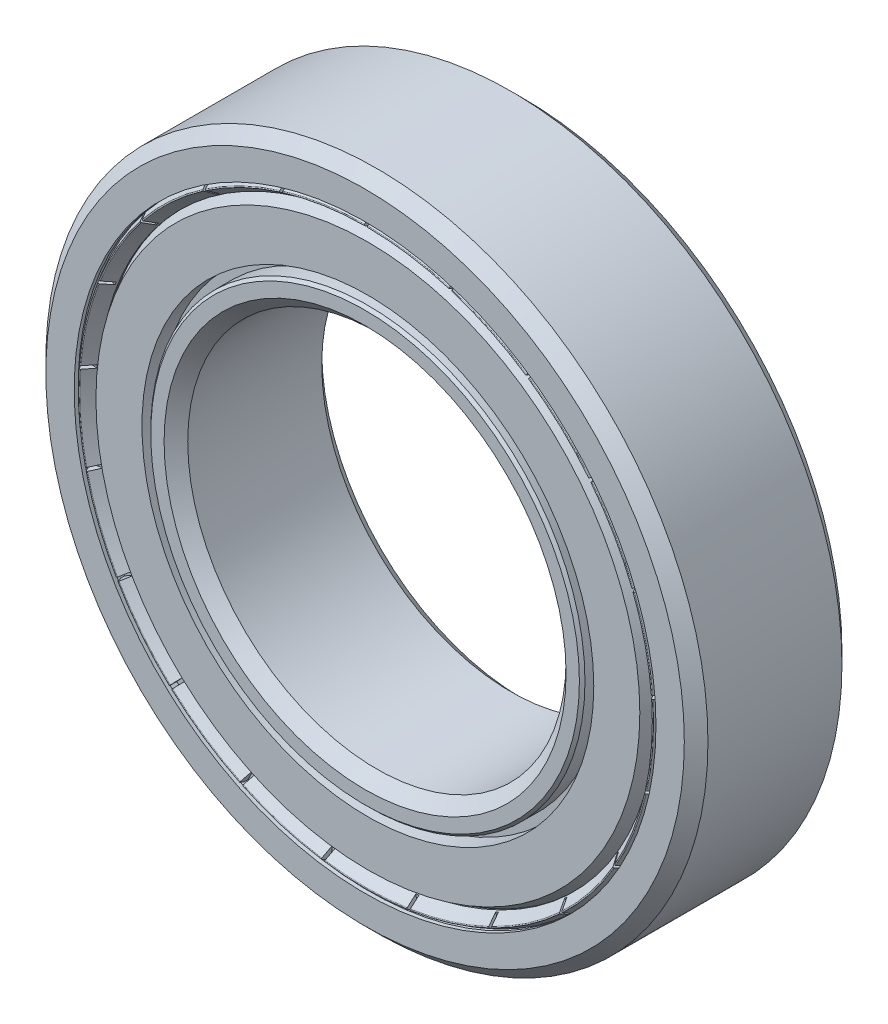
SolidWorks part; units mm, degrees
ref_plane "Front Plane" through (0, 0, 0) normal (0, 0, 1) x (1, 0, 0)
ref_plane "Top Plane" through (0, 0, 0) normal (0, 1, 0) x (1, 0, 0)
ref_plane "Right Plane" through (0, 0, 0) normal (1, 0, 0) x (0, 0, -1)
sketch "Sketch1" plane through (0, 0, 0) normal (0, 0, 1) x (1, 0, 0)
  circle A0 centre (0, 0) radius 6
  circle A1 centre (0, 0) radius 10.5
  dimension "OD" = 21
  dimension "ID" = 12
sketch "Sketch2" plane through (0, 0, 0) normal (1, 0, 0) x (0, 0, -1)
  line L0 (-2.5, 10.5) -> (2.5, 10.5)
  line L1 (-2.5, 6) -> (-2.5, -6) construction
  line L2 (2.5, 10.5) -> (2.5, -10.5) construction
  line L3 (-2.5, 0) -> (2.5, 0) construction
  line L6 (0, 10.5) -> (0, 6) construction
  circle A0 centre (0, 8.25) radius 1.575 construction
  point P8 (0, 10.5)
  dimension "Approx. Ball Dia." = 3.15
  dimension "Width" = 5
  dimension "For Shaft Diameter" = 12
  dimension "For Housing ID" = 21
sketch "Sketch3" plane through (0, 0, 0) normal (1, 0, 0) x (0, 0, -1)
  line L0 (0, 0) -> (0, 12) construction
  line L1 (-2.5, 6) -> (-2.5, -6) construction
  line L2 (2.125, 10.5) -> (-2.125, 10.5)
  line L3 (-2.125, 10.5) -> (-2.5, 10.125)
  line L4 (-2.5, 10.125) -> (-2.5, 9.2262)
  line L5 (-2.5, 9.2262) -> (-2.375, 9.2262)
  line L6 (-2.375, 9.2262) -> (-2.375, 9.5256)
  line L7 (-2.375, 9.5256) -> (-2.2866, 9.614)
  line L8 (-2.2866, 9.614) -> (-0.7875, 9.614)
  line L10 (-2.5, 10.5) -> (2.5, 10.5) construction
  line L12 (-2.375, 9.5256) -> (-2.375, 9.825) construction
  line L13 (2.2866, 9.614) -> (0.7875, 9.614)
  line L14 (2.375, 9.5256) -> (2.2866, 9.614)
  line L15 (2.375, 9.2262) -> (2.375, 9.5256)
  line L16 (2.5, 9.2262) -> (2.375, 9.2262)
  line L17 (2.5, 10.125) -> (2.5, 9.2262)
  line L18 (2.125, 10.5) -> (2.5, 10.125)
  line L19 (2.125, 6) -> (-2.125, 6)
  line L20 (-2.125, 6) -> (-2.5, 6.375)
  line L21 (-2.5, 6.375) -> (-2.5, 6.7976)
  line L22 (-2.5, 6.7976) -> (-2.4116, 6.886)
  line L23 (-2.4116, 6.886) -> (-0.7875, 6.886)
  line L25 (2.4116, 6.886) -> (0.7875, 6.886)
  line L26 (2.5, 6.7976) -> (2.4116, 6.886)
  line L27 (2.5, 6.375) -> (2.5, 6.7976)
  line L28 (2.125, 6) -> (2.5, 6.375)
  circle A2 centre (0, 8.25) radius 1.575 construction
  arc A3 (-0.7875, 9.614) -> (0.7875, 9.614) centre (0, 8.25) cw
  arc A4 (-0.7875, 6.886) -> (0.7875, 6.886) centre (0, 8.25) ccw
  point P5 (0, 9.825)
  point P31 (0, 10.5)
  point P37 (0, 6)
  dimension "D1" = 45
  dimension "D2" = 0.125
  dimension "D3" = 1.575
  dimension "D4" = 0.375
revolve "Revolve1" add sketch "Sketch3" angle 360 about L3
sketch "Sketch4" plane through (0, 0, 0) normal (1, 0, 0) x (0, 0, -1)
  line L0 (0, 9.825) -> (0, 6.675)
  line L1 (0, 10.5) -> (0, 6) construction
  circle A0 centre (0, 8.25) radius 1.575 construction
  arc A1 (0, 6.675) -> (0, 9.825) centre (0, 8.25) cw
revolve "Revolve2" add sketch "Sketch4" angle 360 about L6
pattern_circular "CirPattern1" count 10 over 360 about axis through (0, 0, 2.5) along (0, 0, -1) of bodies 106
sketch "Sketch5" plane through (0, 0, 0) normal (1, 0, 0) x (0, 0, -1)
  line L0 (-1.575, 8.25) -> (-1.575, 6.886) construction
  line L1 (-2.4116, 6.886) -> (-0.7875, 6.886) construction
  line L3 (-1.575, 6.886) -> (-1.8539, 6.886)
  line L4 (-1.8539, 6.886) -> (-1.8539, 7.1649)
  line L5 (-1.8539, 7.1649) -> (-2.4116, 7.1649)
  line L6 (-2.4116, 7.1649) -> (-2.4116, 8.6253)
  line L7 (-2.4116, 8.6253) -> (-1.8539, 8.9473)
  line L8 (-1.8539, 8.9473) -> (-1.575, 8.9473)
  line L9 (-1.575, 8.9473) -> (-1.575, 6.886)
  line L10 (0, 8.25) -> (0, 10.5) construction
  line L11 (1.8539, 8.9473) -> (1.575, 8.9473)
  line L12 (2.4116, 8.6253) -> (1.8539, 8.9473)
  line L13 (2.4116, 7.1649) -> (2.4116, 8.6253)
  line L14 (1.8539, 7.1649) -> (2.4116, 7.1649)
  line L15 (1.8539, 6.886) -> (1.8539, 7.1649)
  line L16 (1.575, 6.886) -> (1.8539, 6.886)
  line L17 (1.575, 8.9473) -> (1.575, 6.886)
  line L18 (-2.4116, 8.6253) -> (-2.1327, 8.6253) construction
  line L19 (-2.1327, 8.6253) -> (-1.8539, 8.6253) construction
  line L20 (-1.8539, 8.6253) -> (-1.575, 8.6253) construction
  line L21 (-1.8539, 8.9473) -> (-1.8539, 9.2262) construction
  circle A0 centre (0, 8.25) radius 1.575 construction
  dimension "D1" = 30
revolve "Revolve3" add sketch "Sketch5" angle 360 about L3
sketch "Sketch6" plane through (0, 0, 0) normal (1, 0, 0) x (0, 0, -1)
  line L0 (-2.0406, 9.2262) -> (-2.2812, 9.2262)
  line L1 (-2.2812, 9.2262) -> (-2.5, 9.0999)
  line L2 (-2.5, 9.0999) -> (-2.1156, 8.8307)
  line L4 (-2.4116, 8.6253) -> (-1.8539, 8.9473) construction
  line L5 (-2.0406, 8.8395) -> (-2.0406, 9.2262)
  line L6 (-2.5, 9.2262) -> (-2.375, 9.2262) construction
  line L7 (-2.1156, 8.8307) -> (-2.0906, 8.8307)
  line L8 (-2.0906, 8.8307) -> (-2.0406, 8.8395)
  line L9 (-2.5, 10.125) -> (-2.5, -10.125) construction
  line L11 (-2.0906, 8.8307) -> (-2.0656, 8.8307) construction
  line L12 (-2.0656, 8.8307) -> (-2.0406, 8.8307) construction
  point P27 (-2.1609, 9.2262)
  dimension "D1" = 30
  dimension "D3" = 10
  dimension "D2" = 35
  dimension "D4" = 0.025
  dimension "D5" = 0.2188
revolve "Revolve4" add sketch "Sketch6" angle 360 about L3
fillet "Fillet1" radius 0.025 1 edges at (9.0999, 0, 2.5)
sketch "Sketch7" plane through (0, 0, 0) normal (0, 0, 1) x (1, 0, 0)
  line L0 (-0.05, 9.2262) -> (-0.05, 9.3262)
  line L1 (-0.05, 9.2262) -> (0.05, 9.2262) construction
  line L2 (-0.05, 9.2262) -> (-0.05, 8.8307)
  line L3 (-0.05, 8.8307) -> (0.05, 8.8307) construction
  line L4 (0.05, 9.2262) -> (0.05, 8.8307)
  line L5 (-0.05, 9.3262) -> (0.05, 9.3262)
  line L6 (0.05, 9.3262) -> (0.05, 9.2262)
  line L7 (-0.05, 8.8307) -> (-0.05, 8.7307)
  line L8 (-0.05, 8.7307) -> (0.05, 8.7307)
  line L9 (0.05, 8.7307) -> (0.05, 8.8307)
  dimension "D1" = 0.1
extrude "Cut-Extrude1" cut sketch "Sketch7" along normal through all from vertex starting at point (0, 9.2262, 2.1609)
pattern_circular "CirPattern2" count 21 over 360 about axis through (0, 0, 2.5) along (0, 0, -1) of "Cut-Extrude1"
mirror "Mirror1" about plane through (0, 0, 0) normal (0, 0, 1) of bodies 120
equation "\"Approx. Ball Dia.@Sketch2\"=( \"OD@Sketch1\" - \"ID@Sketch1\" )  * .5 * .7"
equation "\"D2@Sketch3\"=\"Width@Sketch2\"*.025"
equation "\"D3@Sketch3\"=\"Approx. Ball Dia.@Sketch2\"*.5"
equation "\"D4@Sketch3\"=\"Width@Sketch2\"*.075"
equation "\"Approx No of Balls\"= ( pi * \"OD@Sketch1\" ) * .5 / \"Approx. Ball Dia.@Sketch2\""
equation "\"D1@CirPattern1\"=\"Approx No of Balls\""
equation "\"D4@Sketch6\"=\"D2@Sketch3\"*.2"
equation "\"D1@CirPattern2\"=\"Approx No of Balls\"*2"
equation "\"D5@Sketch6\"=\"D2@Sketch3\"*1.75"
equation "\"D1@Fillet1\"=\"d4@sketch6\""
